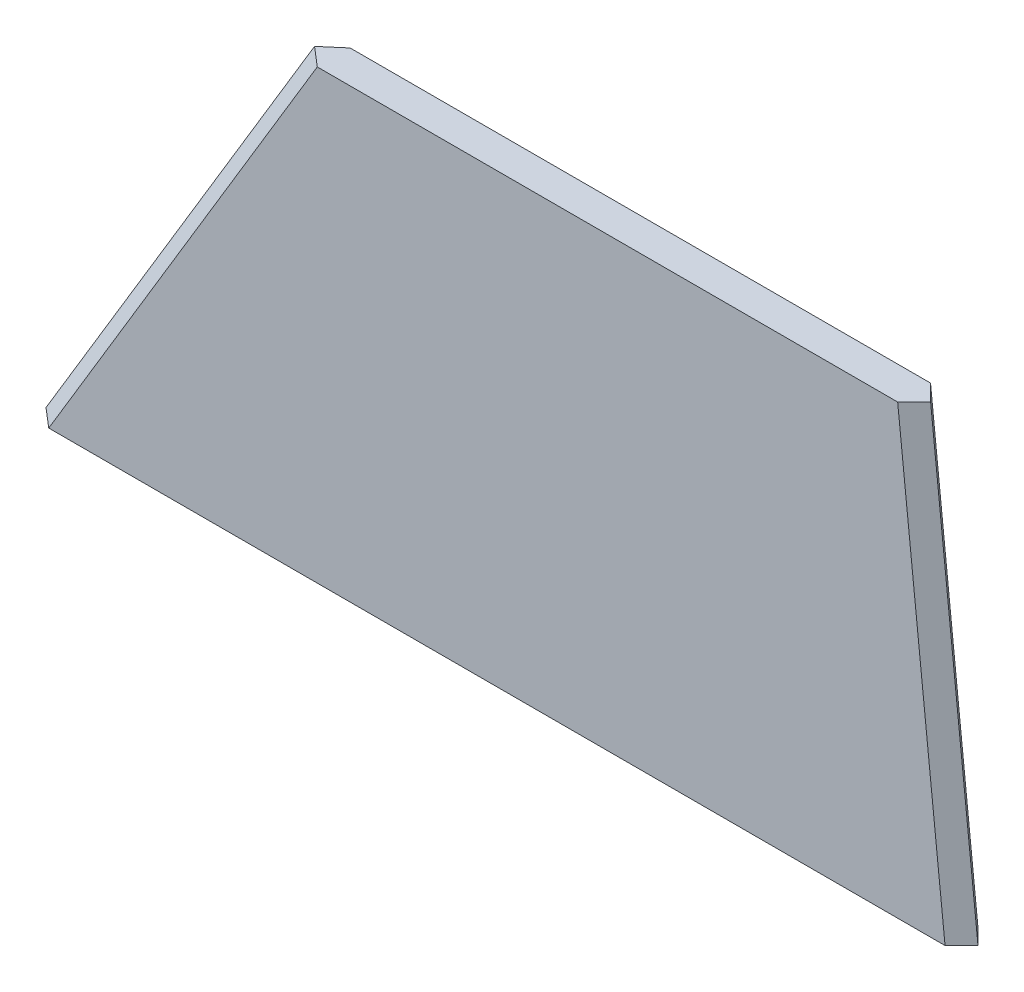
SolidWorks part; units mm, degrees
material "E-Glass Fiber"
ref_plane "Front Plane" through (0, 0, 0) normal (0, 0, 1) x (1, 0, 0)
ref_plane "Top Plane" through (0, 0, 0) normal (0, 1, 0) x (1, 0, 0)
ref_plane "Right Plane" through (0, 0, 0) normal (1, 0, 0) x (0, 0, -1)
sketch "Sketch2" plane through (0, 0, 0) normal (0, 0, 1) x (1, 0, 0)
  line L0 (0, 0) -> (152.4, 0)
  line L1 (152.4, 0) -> (144.78, 71.882)
  line L2 (144.78, 71.882) -> (43.18, 71.882)
  line L3 (43.18, 71.882) -> (0, 0)
  point P3 (184.0643, 71.882)
  dimension "D1" = 71.882
  dimension "D2" = 43.18
  dimension "D3" = 101.6
  dimension "D4" = 152.4
extrude "Boss-Extrude1" add sketch "Sketch2" along normal blind 5.2832
chamfer "Chamfer3" distance 3.81 angle 45 4 edges at (148.59, 35.941, 5.2832) (148.59, 35.941, 0) (21.59, 35.941, 5.2832) (21.59, 35.941, 0)
